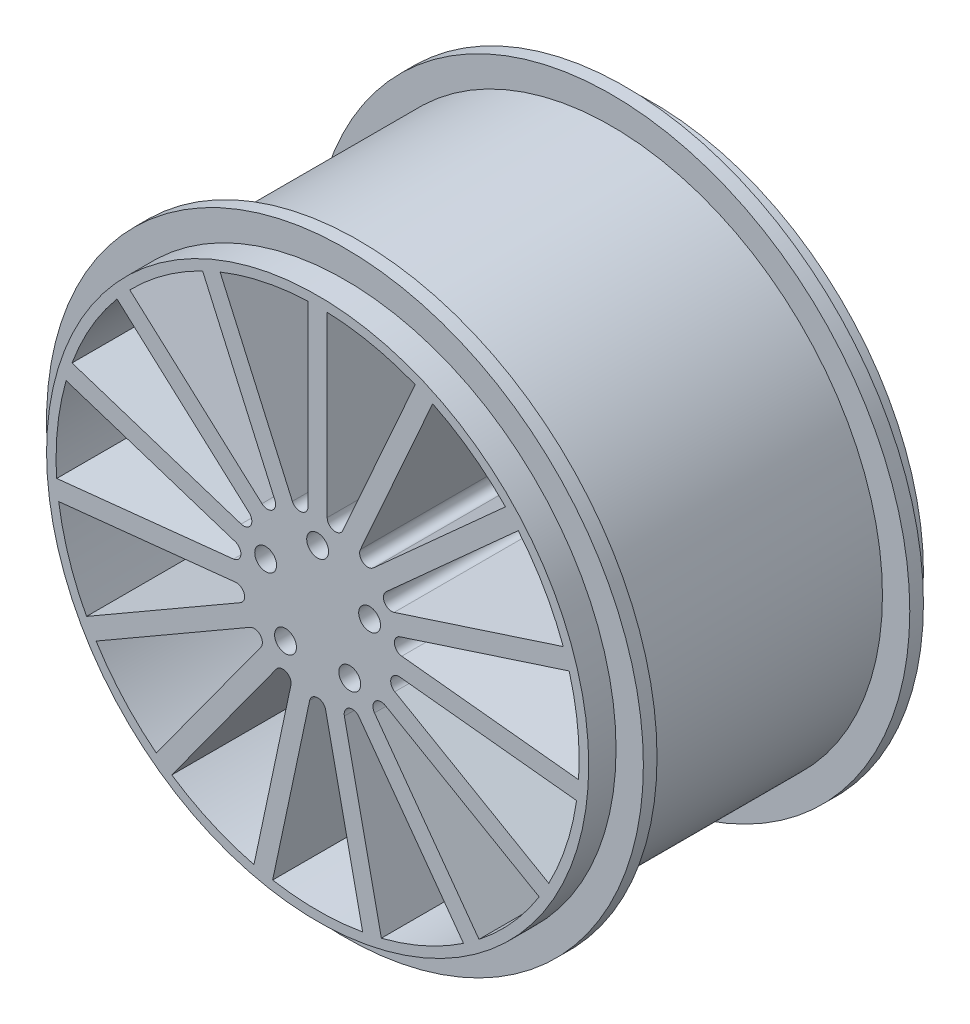
SolidWorks part; units mm, degrees
material "1100-H26 barra (SS)"
ref_plane "Piano frontale" through (0, 0, 0) normal (0, 0, 1) x (1, 0, 0)
ref_plane "Piano superiore" through (0, 0, 0) normal (0, 1, 0) x (1, 0, 0)
ref_plane "Piano destro" through (0, 0, 0) normal (1, 0, 0) x (0, 0, -1)
sketch "Schizzo1" plane through (0, 0, 0) normal (0, 0, 1) x (1, 0, 0)
  line L0 (0, 0) -> (0, 198.425)
  line L1 (80.7067, 181.2703) -> (0, 0)
  line L2 (7, 61.1602) -> (7, 191.297)
  line L3 (71.4127, 177.6056) -> (18.4813, 58.7198)
  line L4 (7, 32.9324) -> (7, 191.297) construction
  line L5 (71.4127, 177.6056) -> (7, 32.9324) construction
  arc A0 (0, 198.425) -> (80.7067, 181.2703) centre (0, 0) cw
  arc A1 (7, 191.297) -> (71.4127, 177.6056) centre (0, 0) cw
  arc A2 (7, 61.1602) -> (18.4813, 58.7198) centre (13, 61.1602) ccw
  dimension "D3" = 6
  dimension "D1" = 198.425
  dimension "D2" = 7
extrude "Estrusione-Estrusione2" add sketch "Schizzo1" along normal blind 165
pattern_circular "RipetizioneCircolare1" count 15 over 360 about axis through (0, 0, 165) along (0, 0, -1) of "Estrusione-Estrusione2" reverse direction yes
sketch "Schizzo6" plane through (0, 0, 165) normal (0, 0, 1) x (1, 0, 0)
  circle A0 centre (0, 40) radius 8
  dimension "D1" = 40
extrude "Taglio-Estrusione1" cut sketch "Schizzo6" against normal through all
pattern_circular "RipetizioneCircolare2" count 5 over 360 about axis through (0, 0, 165) along (0, 0, 1) of "Taglio-Estrusione1"
sketch "Schizzo7" plane through (0, 0, 0) normal (0, 0, -1) x (-1, 0, 0)
  circle A0 centre (0, 0) radius 198.425
  circle A1 centre (0, 0) radius 191.425
  dimension "D1" = 7
extrude "Estrusione-Estrusione4" add sketch "Schizzo7" along normal blind 80
sketch "Schizzo8" plane through (0, 0, 0) normal (1, 0, 0) x (0, 0, -1)
  line L0 (80, 198.425) -> (-165, 198.425) construction
  line L1 (-135, 198.425) -> (-145, 198.425)
  line L2 (-135, 198.425) -> (-135, 218.425)
  line L3 (-135, 218.425) -> (-145, 218.425)
  line L4 (-145, 198.425) -> (-145, 218.425)
  line L5 (50, 198.425) -> (60, 198.425)
  line L6 (50, 198.425) -> (50, 218.425)
  line L7 (50, 218.425) -> (60, 218.425)
  line L8 (60, 198.425) -> (60, 218.425)
  line L9 (80, -198.425) -> (80, 198.425) construction
  line L11 (0, 0) -> (366.145, 0) construction
  line L13 (-165, 198.425) -> (-165, -198.425) construction
  dimension "D1" = 20
  dimension "D2" = 20
  dimension "D3" = 10
  dimension "D4" = 20
  dimension "D5" = 10
  dimension "D6" = 20
revolve "Rivoluzione1" add sketch "Schizzo8" angle 360 about L11
